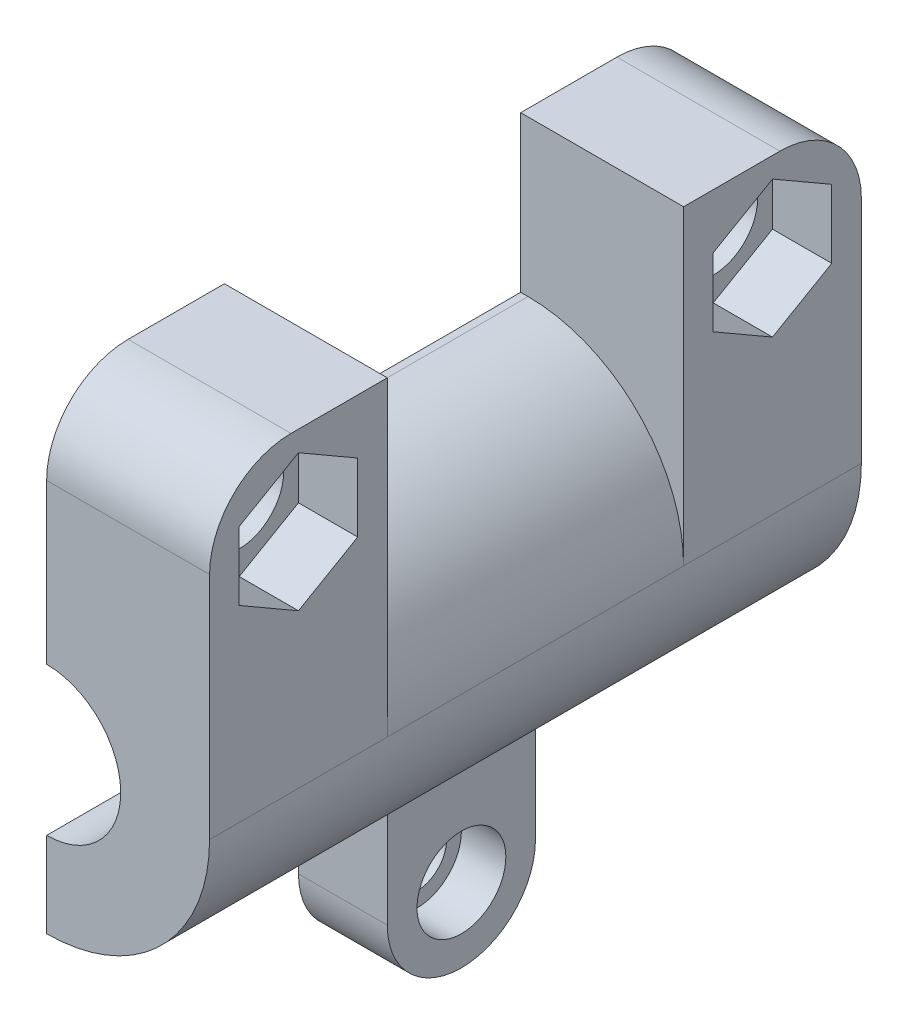
SolidWorks part; units mm, degrees
ref_plane "Front Plane" through (0, 0, 0) normal (0, 0, 1) x (1, 0, 0)
ref_plane "Top Plane" through (0, 0, 0) normal (0, 1, 0) x (1, 0, 0)
ref_plane "Right Plane" through (0, 0, 0) normal (1, 0, 0) x (0, 0, -1)
sketch "Sketch1" plane through (0, 0, 0) normal (1, 0, 0) x (0, 0, -1)
  line L1 (-22, -16) -> (22, -16)
  line L2 (-22, -16) -> (-22, 16)
  line L3 (-22, 16) -> (22, 16)
  line L4 (22, -16) -> (22, 16)
  line L5 (-22, -16) -> (22, 16) construction
  line L6 (-22, 16) -> (22, -16) construction
  point P0 (0, 0)
  dimension "D1" = 44
  dimension "D2" = 32
extrude "Boss-Extrude1" add sketch "Sketch1" along normal blind 11
sketch "Sketch2" plane through (0, 0, 0) normal (1, 0, 0) x (0, 0, -1)
  line L0 (-22, -16) -> (22, -16) construction
  line L1 (12.25, -13) -> (-12.25, -13)
  line L2 (12.25, -13) -> (12.25, 2.5)
  line L3 (12.25, 2.5) -> (-12.25, 2.5)
  line L4 (-12.25, -13) -> (-12.25, 2.5)
  line L5 (12.25, -13) -> (-12.25, 2.5) construction
  line L6 (12.25, 2.5) -> (-12.25, -13) construction
  point P0 (0, -5.25)
  dimension "D1" = 24.5
  dimension "D2" = 15.5
  dimension "D3" = 0
  dimension "D4" = 3
extrude "Cut-Extrude1" cut sketch "Sketch2" along normal blind 7.75 contours L2 L1 L4 L3
fillet "Fillet1" radius 7.75 2 edges at (7.75, 2.5, 0) (7.75, -13, 0)
sketch "Sketch3" plane through (0, 0, -12.25) normal (0, 0, 1) x (1, 0, 0)
  arc A0 (0, -13) -> (7.75, -5.25) centre (0, -5.25) ccw construction
  arc A1 (0, -13) -> (7.75, -5.25) centre (0, -5.25) ccw
  circle A2 centre (0, -5.25) radius 5
  line M3 (0, 2.5) -> (0, -13)
  dimension "D1" = 10
extrude "Cut-Extrude2" cut sketch "Sketch3" against normal through all both and the other way through all contours A2 M3 | A2 M3 region at (2.1221, -5.25, -12.25) region at (-2.1221, -5.25, -12.25)
sketch "Sketch4" plane through (11, 0, 0) normal (1, 0, 0) x (0, 0, -1)
  line L0 (22, 16) -> (-22, 16) construction
  line L2 (-10, 16) -> (10, 16)
  line L3 (-10, 16) -> (-10, 5.5)
  line L4 (-10, 5.5) -> (10, 5.5)
  line L5 (10, 16) -> (10, 5.5)
  circle A0 centre (-16, 10) radius 3
  circle A1 centre (16, 10) radius 3
  dimension "D1" = 6
  dimension "D2" = 6
  dimension "D3" = 6
  dimension "D4" = 6
  dimension "D5" = 6
  dimension "D6" = 6
  dimension "D7" = 32
  dimension "D8" = 10
  dimension "D9" = 10.5
extrude "Cut-Extrude3" cut sketch "Sketch4" against normal through all
sketch "Sketch5" plane through (11, 0, 0) normal (1, 0, 0) x (0, 0, -1)
  line L0 (-16, 10) -> (-16, 4.5)
  line L1 (-2.75, -3) -> (2.75, -3)
  line L2 (-2.75, -3) -> (-2.75, 0)
  line L3 (-2.75, 0) -> (2.75, 0)
  line L4 (2.75, -3) -> (2.75, 0)
  line L5 (-2.75, -3) -> (2.75, 0) construction
  line L6 (-2.75, 0) -> (2.75, -3) construction
  line L7 (16, 10) -> (16, 4.5)
  line L8 (-2.75, 0) -> (-16, 4.5)
  line L9 (2.75, 0) -> (16, 4.5)
  line L10 (2.75, -3) -> (16, 4.5)
  line L11 (-2.75, -3) -> (-16, 4.5)
  line L12 (16, 4.5) -> (16, -3)
  line L13 (16, -3) -> (2.75, -3)
  line L14 (-2.75, -3) -> (-16, -3)
  line L15 (-16, -3) -> (-16, 4.5)
  circle A0 centre (16, 10) radius 3 construction
  circle A1 centre (16, 10) radius 3
  circle A2 centre (-16, 10) radius 3 construction
  circle A3 centre (-16, 10) radius 3
  point P0 (0, -1.5)
  dimension "D1" = 10
  dimension "D2" = 3
  dimension "D3" = 5.5
  dimension "D4" = 0
  dimension "D5" = 5.5
  dimension "D6" = 5.5
extrude "Boss-Extrude4" [suppressed] add sketch "Sketch5" along normal blind 7 contours L15 L14 L11 | L11 L2 L8 | L1 L4 L3 L2 | L4 L10 L9 | L13 L12 L10
chamfer "Chamfer1" [suppressed] distance 7 angle 45
sketch "Sketch6" [suppressed] plane through (12, 0, 0) normal (1, 0, 0) x (0, 0, -1)
  line L0 (16, -3) -> (-16, -3) construction
  line L1 (16, -3) -> (-16, -3)
  line L2 (16, -10) -> (-16, -10) construction
  line L3 (-13, -3) -> (13, -3)
  line L4 (-13, -3) -> (-13, -10)
  line L5 (-13, -10) -> (13, -10)
  line L6 (13, -3) -> (13, -10)
  line L7 (-16, -10) -> (-16, -3) construction
  line L8 (10, 5.5) -> (-10, 5.5)
  line L9 (-10, 5.5) -> (-10, 16)
  line L10 (-10, 16) -> (-22, 16)
  line L11 (-22, 16) -> (-22, -16)
  line L12 (-22, -16) -> (22, -16)
  line L13 (22, -16) -> (22, 16)
  line L14 (22, 16) -> (10, 16)
  line L15 (10, 16) -> (10, 5.5)
  line L16 (10, 5.5) -> (-10, 5.5)
  line L17 (-10, 5.5) -> (-10, 16)
  line L18 (-10, 16) -> (-22, 16)
  line L19 (-22, 16) -> (-22, -16)
  line L20 (-22, -16) -> (22, -16)
  line L21 (22, -16) -> (22, 16)
  line L22 (22, 16) -> (10, 16)
  line L23 (10, 16) -> (10, 5.5)
  line L24 (16, 4.5) -> (16, -10) construction
  line L25 (-2.75, 0) -> (2.75, 0) construction
  line L26 (-1.5, -3) -> (1.5, -3)
  line L27 (-1.5, -3) -> (-1.5, -10)
  line L28 (-1.5, -10) -> (1.5, -10)
  line L29 (1.5, -3) -> (1.5, -10)
  point P26 (0, 0)
  line M13 (16, -10) -> (-16, -10)
  dimension "D2" = 3
  dimension "D3" = 3
  dimension "D4" = 3
  dimension "D5" = 1.5
  dimension "D1" = 0
extrude "Cut-Extrude5" [suppressed] cut sketch "Sketch6" along normal through all contours L27 L1 L4 L5 | L1 L29 L6 M13
fillet "Fillet4" radius 5.5 2 edges at (5.5, 16, -22) (5.5, 16, 22)
sketch "Sketch7" plane through (0, 0, 0) normal (1, 0, 0) x (0, 0, -1)
  line L0 (-22, -16) -> (22, -16) construction
  line L1 (5, -16) -> (-5, -16)
  line L2 (5, -16) -> (5, -26)
  line L3 (5, -26) -> (-5, -26)
  line L4 (-5, -16) -> (-5, -26)
  circle A0 centre (0, -21) radius 2
  dimension "D4" = 4
  dimension "D1" = 10
  dimension "D2" = 10
  dimension "D3" = 5
  dimension "D5" = 5
extrude "Boss-Extrude5" add sketch "Sketch7" along normal blind 6
sketch "Sketch8" plane through (6, 0, 0) normal (1, 0, 0) x (0, 0, -1)
  line L1 (0, -24.1754) -> (2.75, -22.5877)
  line L2 (2.75, -22.5877) -> (2.75, -19.4123)
  line L3 (2.75, -19.4123) -> (0, -17.8246)
  line L4 (0, -17.8246) -> (-2.75, -19.4123)
  line L5 (-2.75, -19.4123) -> (-2.75, -22.5877)
  line L6 (-2.75, -22.5877) -> (0, -24.1754)
  circle A0 centre (0, -21) radius 2 construction
  circle A1 centre (0, -21) radius 2
  circle A2 centre (0, -21) radius 2.75 construction
  dimension "D1" = 5.5
extrude "Cut-Extrude6" [suppressed] cut sketch "Sketch8" against normal blind 2
fillet "Fillet5" radius 5 2 edges at (3, -26, -5) (3, -26, 5)
sketch "Sketch9" plane through (6, 0, 0) normal (1, 0, 0) x (0, 0, -1)
  circle A0 centre (0, -21) radius 2 construction
  circle A1 centre (0, -21) radius 2
  circle A2 centre (0, -21) radius 3
  dimension "D1" = 6
extrude "Cut-Extrude7" cut sketch "Sketch9" against normal blind 3
sketch "Sketch10" plane through (11, 0, 0) normal (1, 0, 0) x (0, 0, -1)
  line L1 (-16, 5.3812) -> (-12, 7.6906)
  line L2 (-12, 7.6906) -> (-12, 12.3094)
  line L3 (-12, 12.3094) -> (-16, 14.6188)
  line L4 (-16, 14.6188) -> (-20, 12.3094)
  line L5 (-20, 12.3094) -> (-20, 7.6906)
  line L6 (-20, 7.6906) -> (-16, 5.3812)
  line L7 (16, 5.3812) -> (20, 7.6906)
  line L8 (20, 7.6906) -> (20, 12.3094)
  line L9 (20, 12.3094) -> (16, 14.6188)
  line L10 (16, 14.6188) -> (12, 12.3094)
  line L11 (12, 12.3094) -> (12, 7.6906)
  line L12 (12, 7.6906) -> (16, 5.3812)
  circle A0 centre (16, 10) radius 3 construction
  circle A1 centre (-16, 10) radius 3 construction
  circle A2 centre (16, 10) radius 3
  circle A3 centre (-16, 10) radius 3
  circle A4 centre (-16, 10) radius 4 construction
  circle A5 centre (16, 10) radius 4 construction
  dimension "D1" = 8
  dimension "D2" = 8
extrude "Cut-Extrude8" cut sketch "Sketch10" against normal blind 4
fillet "Fillet7" radius 10.5 1 edges at (11, 5.5, 0)
fillet "Fillet8" radius 11 1 edges at (11, -16, 0)
